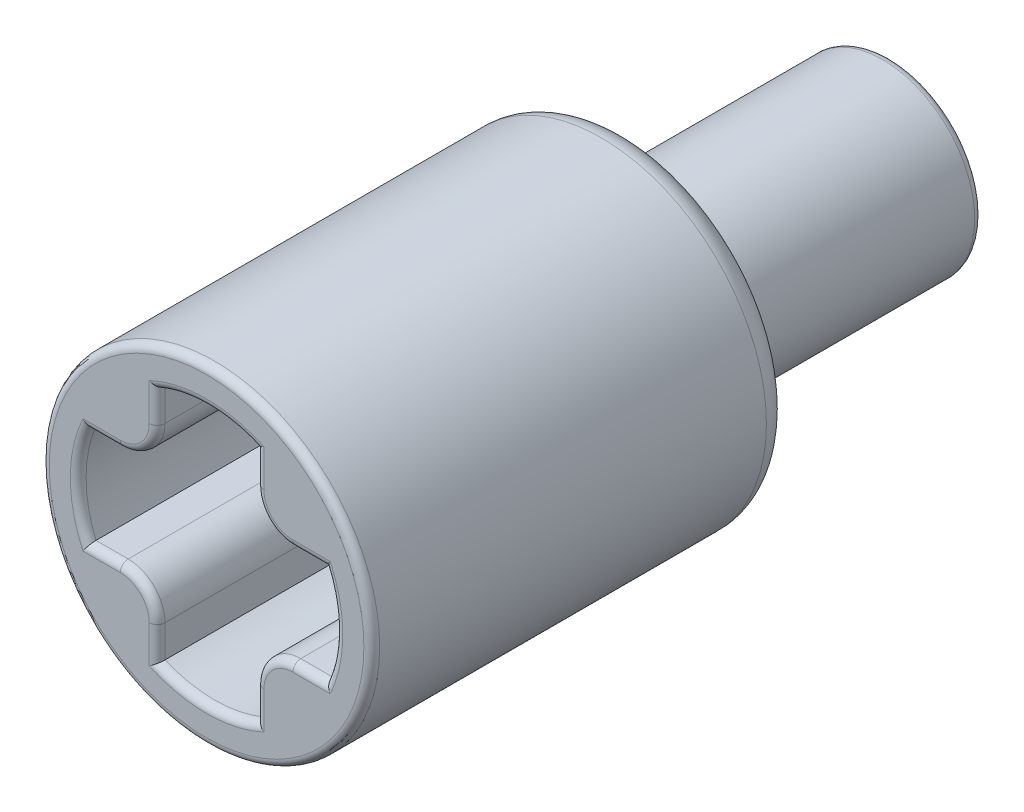
SolidWorks part; units mm, degrees
ref_plane "Front Plane" through (0, 0, 0) normal (0, 0, 1) x (1, 0, 0)
ref_plane "Top Plane" through (0, 0, 0) normal (0, 1, 0) x (1, 0, 0)
ref_plane "Right Plane" through (0, 0, 0) normal (1, 0, 0) x (0, 0, -1)
sketch "Sketch1" plane through (0, 0, 0) normal (0, 0, 1) x (1, 0, 0)
  circle A0 centre (0, 0) radius 1
  circle A1 centre (0, 0) radius 1.75
  dimension "D1" = 2
  dimension "D2" = 0.75
extrude "Boss-Extrude1" add sketch "Sketch1" along normal blind 5
sketch "Sketch2" plane through (0, 0, 5) normal (0, 0, 1) x (1, 0, 0)
  line L0 (0.89, 0.89) -> (0.89, 2.2181) construction
  line L1 (0.89, 0.89) -> (2.2181, 0.89) construction
  line L2 (2.2181, -0.89) -> (0.89, -0.89) construction
  line L3 (0.89, -0.89) -> (0.89, -2.2181) construction
  line L4 (-0.89, -2.2181) -> (-0.89, -0.89) construction
  line L5 (-0.89, -0.89) -> (-2.2181, -0.89) construction
  line L6 (-2.2181, 0.89) -> (-0.89, 0.89) construction
  line L7 (-0.89, 0.89) -> (-0.89, 2.2181) construction
  line L8 (0.94, 0.94) -> (2.2517, 0.94)
  line L9 (0.94, 0.94) -> (0.94, 2.2517)
  line L10 (-0.94, 0.94) -> (-0.94, 2.2517)
  line L11 (-2.2517, 0.94) -> (-0.94, 0.94)
  line L12 (-0.94, -0.94) -> (-2.2517, -0.94)
  line L13 (-0.94, -2.2517) -> (-0.94, -0.94)
  line L14 (0.94, -0.94) -> (0.94, -2.2517)
  line L15 (2.2517, -0.94) -> (0.94, -0.94)
  circle A0 centre (0, 0) radius 3.14
  circle A1 centre (0, 0) radius 1.75
  circle A2 centre (0, 0) radius 1.75
  arc A3 (-0.89, 2.2181) -> (0.89, 2.2181) centre (0, 0) cw construction
  arc A4 (-2.2181, 0.89) -> (-2.2181, -0.89) centre (0, 0) ccw construction
  arc A5 (-0.89, -2.2181) -> (0.89, -2.2181) centre (0, 0) ccw construction
  arc A6 (2.2181, -0.89) -> (2.2181, 0.89) centre (0, 0) ccw construction
  arc A7 (2.2517, -0.94) -> (2.2517, 0.94) centre (0, 0) ccw
  arc A8 (-0.94, 2.2517) -> (0.94, 2.2517) centre (0, 0) cw
  arc A9 (-2.2517, 0.94) -> (-2.2517, -0.94) centre (0, 0) ccw
  arc A10 (-0.94, -2.2517) -> (0.94, -2.2517) centre (0, 0) ccw
  line B0 (-0.89, 2.2181) -> (-0.89, 0.89) construction
  line B1 (-0.89, 0.89) -> (-2.2181, 0.89) construction
  line B2 (0.89, 2.2181) -> (0.89, 0.89) construction
  line B3 (0.89, 0.89) -> (2.2181, 0.89) construction
  line B4 (-2.2181, -0.89) -> (-0.89, -0.89) construction
  line B5 (-0.89, -0.89) -> (-0.89, -2.2181) construction
  line B6 (0.89, -2.2181) -> (0.89, -0.89) construction
  line B7 (0.89, -0.89) -> (2.2181, -0.89) construction
  arc B8 (-0.89, 2.2181) -> (0.89, 2.2181) centre (0, 0) cw construction
  arc B9 (-2.2181, 0.89) -> (-2.2181, -0.89) centre (0, 0) ccw construction
  arc B10 (2.2181, 0.89) -> (2.2181, -0.89) centre (0, 0) cw construction
  arc B11 (-0.89, -2.2181) -> (0.89, -2.2181) centre (0, 0) ccw construction
  circle M23 centre (0, 0) radius 1.75
  circle M24 centre (0, 0) radius 1
  dimension "D2" = 0.75
  dimension "D1" = 0
  dimension "D3" = 0.05
sketch_block_instance "Lego Axle - Unfilleted-1"
sketch_block "Lego Axle - Unfilleted"
extrude "Boss-Extrude2" add sketch "Sketch2" along normal blind 1 contours A0 A10 L13 L12 A9 L11 L10 A8 L9 L8 A7 L15 L14 M23 | L11 L10 M23 | L11 A9 L12 M23 | L15 L8 L9 L10 L11 L12 L13 L14 M23 M24 | M24 | A8 L10 L9 M23 | L9 L8 M23 | L15 A7 L8 M23 | L15 L14 M23 | L13 A10 L14 M23 | L13 L12 M23 region at (1.1316, 1.1316, 5) region at (1.2081, 0.8905, 5) region at (2.0176, 0, 5) region at (0, 2.0176, 5) region at (-1.1316, 1.1316, 5) region at (1.1316, -1.1316, 5) region at (-2.0176, 0, 5) region at (0, -2.0176, 5) region at (-1.1316, -1.1316, 5) region at (-3.0512, 0, 5) region at (0, 0, 5)
extrude "Boss-Extrude3" add sketch "Sketch2<4>" along normal blind 8 contours A0 A10 L13 L12 A9 L11 L10 A8 L9 L8 A7 L15 L14 M23 | L11 L10 M23 | L9 L8 M23 | L15 L14 M23 | L13 L12 M23 region at (1.1316, 1.1316, 5) region at (-1.1316, 1.1316, 5) region at (1.1316, -1.1316, 5) region at (-1.1316, -1.1316, 5) region at (-3.0512, 0, 5)
sketch "Sketch2<4>" plane through (0, 0, 5) normal (0, 0, 1) x (1, 0, 0) same geometry as "Sketch2"
fillet "Fillet1" radius 0.5 2 edges at (3.14, 0, 5) (1.75, 0, 5)
fillet "Fillet2" radius 0.7 4 edges at (-0.94, 0.94, 9.5) (0.94, 0.94, 9.5) (0.94, -0.94, 9.5) (-0.94, -0.94, 9.5)
fillet "Fillet3" radius 0.15 2 edges at (1.75, 0, 0) (1, 0, 0)
fillet "Fillet4" radius 0.15 17 edges at (-0.94, -1.9458, 13) (-1.145, -1.145, 13) (-1.9458, 0.94, 13) (-1.145, 1.145, 13) (0.94, -1.9458, 13) (1.145, -1.145, 13) (1.9458, 0.94, 13) (1.145, 1.145, 13) (0, -2.44, 13) (-1.9458, -0.94, 13) (-2.44, 0, 13) (-0.94, 1.9458, 13) (0, 2.44, 13) (2.44, 0, 13) (1.9458, -0.94, 13) (0.94, 1.9458, 13) (3.14, 0, 13)
